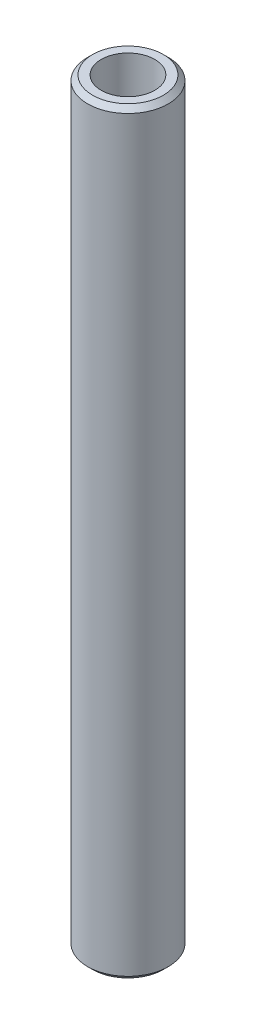
SolidWorks part; units mm, degrees
ref_plane "Front Plane" through (0, 0, 0) normal (0, 0, 1) x (1, 0, 0)
ref_plane "Top Plane" through (0, 0, 0) normal (0, 1, 0) x (1, 0, 0)
ref_plane "Right Plane" through (0, 0, 0) normal (1, 0, 0) x (0, 0, -1)
sketch "Sketch1" plane through (0, 0, 0) normal (0, 1, 0) x (1, 0, 0)
  circle A0 centre (0, 0) radius 12.5
  dimension "SHAFT_OD" = 25
extrude "Boss-Extrude1" add sketch "Sketch1" along normal blind 234.682
sketch "Sketch2" plane through (0, 0, 0) normal (0, 1, 0) x (1, 0, 0)
  circle A0 centre (0, 0) radius 8.3087
  dimension "BORE_D" = 16.6174
extrude "Cut-Extrude1" cut sketch "Sketch2" along normal through all
chamfer "Chamfer1" distance 1.5427 angle 45 2 edges at (0, 234.682, 12.5) (0, 0, 12.5)
